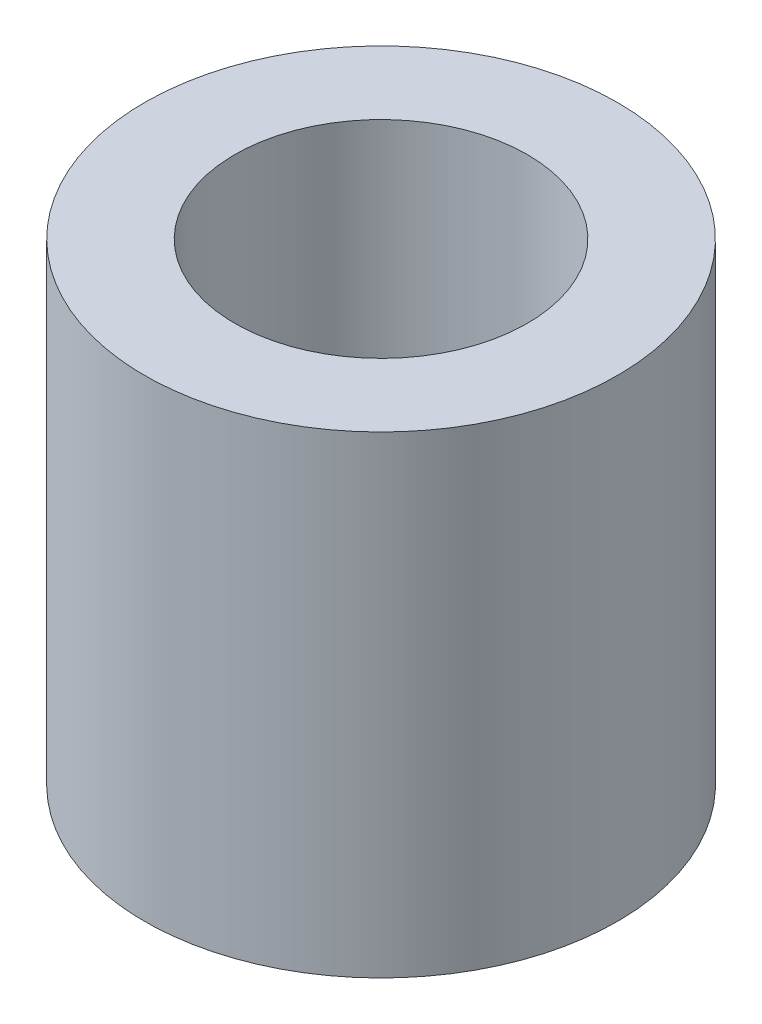
SolidWorks part; units mm, degrees
ref_plane "Front Plane" through (0, 0, 0) normal (0, 0, 1) x (1, 0, 0)
ref_plane "Top Plane" through (0, 0, 0) normal (0, 1, 0) x (1, 0, 0)
ref_plane "Right Plane" through (0, 0, 0) normal (1, 0, 0) x (0, 0, -1)
sketch "Sketch1" plane through (0, 0, 0) normal (0, 1, 0) x (1, 0, 0)
  circle A0 centre (0, 0) radius 2.3813
  circle A1 centre (0, 0) radius 1.4732
  dimension "D1" = 4.7625
  dimension "D2" = 2.9464
extrude "Boss-Extrude1" add sketch "Sketch1" along normal blind 4.7625
